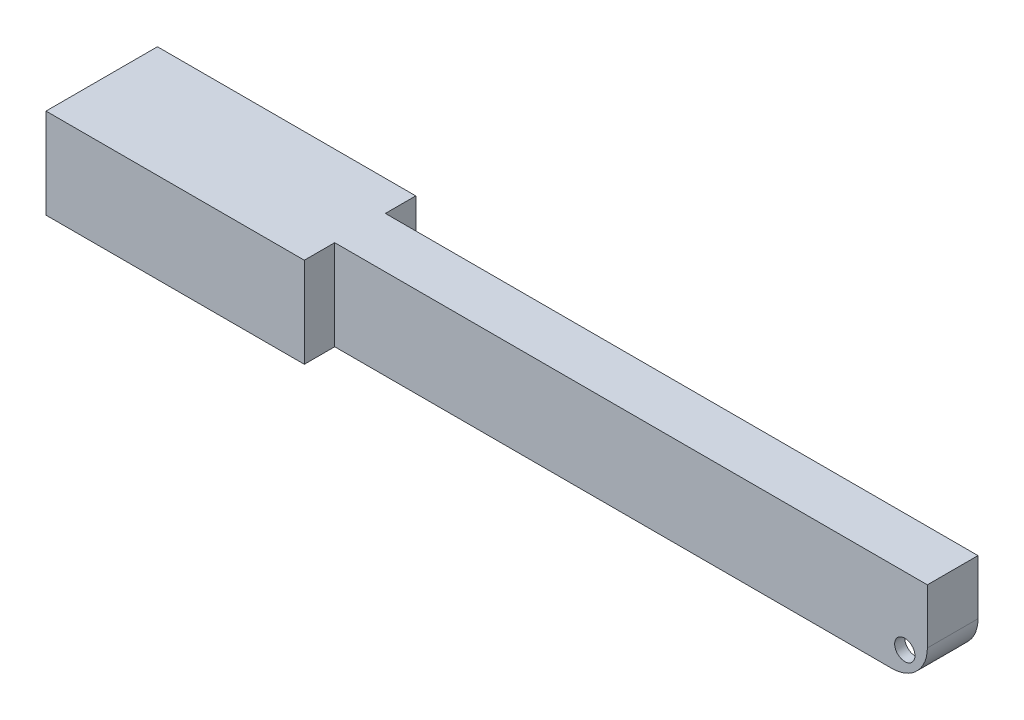
SolidWorks part; units mm, degrees
ref_plane "Front Plane" through (0, 0, 0) normal (0, 0, 1) x (1, 0, 0)
ref_plane "Top Plane" through (0, 0, 0) normal (0, 1, 0) x (1, 0, 0)
ref_plane "Right Plane" through (0, 0, 0) normal (1, 0, 0) x (0, 0, -1)
sketch "Sketch1" plane through (0, 0, 0) normal (0, 1, 0) x (1, 0, 0)
  line L1 (-84, -11) -> (84, -11)
  line L2 (-84, -11) -> (-84, 11)
  line L3 (-84, 11) -> (84, 11)
  line L4 (84, -11) -> (84, 11)
  line L5 (-84, -11) -> (84, 11) construction
  line L6 (-84, 11) -> (84, -11) construction
  point P0 (0, 0)
  dimension "D1" = 22
  dimension "D2" = 168
extrude "Boss-Extrude1" add sketch "Sketch1" against normal blind 17.8 contours L2 L3 L4 L1
sketch "Sketch8" plane through (0, 0, 11) normal (0, 0, 1) x (1, 0, 0)
  line L0 (84, 0) -> (66.2, -17.8) construction
  line L1 (-84, -17.8) -> (84, -17.8) construction
  line L2 (66.2, -17.8) -> (84, -17.8) construction
  line L3 (75.1, -8.9) -> (84, -8.9) construction
  line L4 (84, -17.8) -> (84, 0) construction
  line L5 (79.55, -8.9) -> (79.55, -17.8) construction
  circle A0 centre (79.55, -13.35) radius 2
  dimension "D1" = 4
extrude "Cut-Extrude4" cut sketch "Sketch8" against normal up to surface (22 mm away) up to face at (0, -8.9, -11)
sketch "Sketch5" plane through (0, 0, 0) normal (0, 1, 0) x (1, 0, 0)
  line L0 (-84, 11) -> (84, 11) construction
  line L1 (-33, 11) -> (84, 11)
  line L2 (-33, 11) -> (-33, 5)
  line L3 (-33, 5) -> (84, 5)
  line L4 (84, 11) -> (84, 5)
  line L5 (-33, 11) -> (84, 5) construction
  line L6 (-33, 5) -> (84, 11) construction
  line L7 (84, -11) -> (84, 11) construction
  line L8 (-84, -11) -> (84, -11) construction
  line L9 (-33, -11) -> (84, -11)
  line L10 (-33, -11) -> (-33, -5)
  line L11 (-33, -5) -> (84, -5)
  line L12 (84, -11) -> (84, -5)
  line L13 (-33, -11) -> (84, -5) construction
  line L14 (-33, -5) -> (84, -11) construction
  point P0 (25.5, 8)
  point P9 (25.5, -8)
  dimension "D1" = 117
  dimension "D2" = 6
extrude "Cut-Extrude2" cut sketch "Sketch5" against normal up to surface (17.8 mm away) up to face at (0, -17.8, 0)
sketch "Sketch6" plane through (0, -17.8, 0) normal (0, -1, 0) x (1, 0, 0)
  line L0 (-82, 9) -> (-82, -9)
  line L1 (-82, -9) -> (-35, -9)
  line L2 (-35, -9) -> (-35, -3)
  line L3 (-35, -3) -> (82, -3)
  line L5 (-35, 9) -> (-82, 9)
  line L6 (-84, 11) -> (-33, 11) construction
  line L7 (-84, 11) -> (-84, -11) construction
  line L8 (-84, -11) -> (-33, -11) construction
  line L9 (-33, -5) -> (-33, -11) construction
  line L10 (84, -5) -> (-33, -5) construction
  line L12 (-35, 9) -> (-35, 3)
  line L13 (-35, 3) -> (82, 3)
  line L14 (82, 3) -> (82, -3)
  line L15 (84, 5) -> (84, -5) construction
  line L16 (-33, 5) -> (84, 5) construction
  dimension "D1" = 2
  dimension "D2" = 2
  dimension "D3" = 2
  dimension "D4" = 2
  dimension "D5" = 2
  dimension "D6" = 2
  dimension "D7" = 2
extrude "Cut-Extrude3" cut sketch "Sketch6" against normal offset from surface (15.8 mm away) 2 up to face at (-16.5, 0, 0)
sketch "Sketch7" plane through (0, 0, -9) normal (0, 0, 1) x (1, 0, 0)
  line L0 (-82, -12.3) -> (-35, -12.3)
  line L1 (-82, -12.3) -> (-82, -14.3)
  line L2 (-35, -12.3) -> (-35, -14.3)
  line L3 (-82, -14.3) -> (-35, -14.3)
  line L4 (-82, -2) -> (-82, -17.8) construction
  line L5 (-35, -2) -> (-35, -17.8) construction
  line L7 (-82, -17.8) -> (-35, -17.8) construction
  dimension "D1" = 3.5
  dimension "D2" = 2
extrude "Boss-Extrude3" add sketch "Sketch7" along normal up to surface (18 mm away) up to face at (-58.5, -9.9, 9)
fillet "Fillet1" radius 7 1 edges at (84, -17.8, 0)
